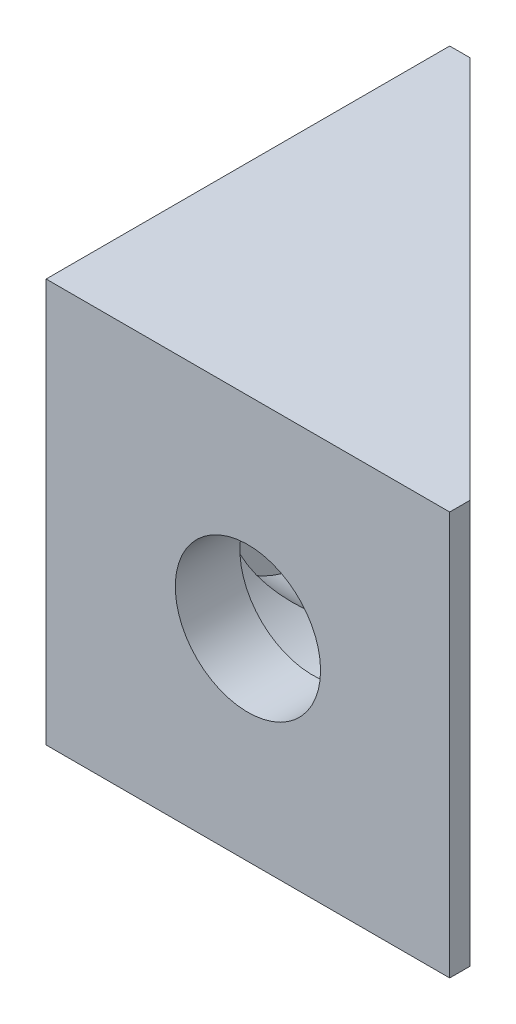
SolidWorks part; units mm, degrees
ref_plane "Front Plane" through (0, 0, 0) normal (0, 0, 1) x (1, 0, 0)
ref_plane "Top Plane" through (0, 0, 0) normal (0, 1, 0) x (1, 0, 0)
ref_plane "Right Plane" through (0, 0, 0) normal (1, 0, 0) x (0, 0, -1)
sketch "Sketch2" plane through (0, 0, 0) normal (0, 1, 0) x (1, 0, 0)
  line L0 (0, 0) -> (0, 20)
  line L2 (20, 0) -> (0, 0)
  line L3 (0, 20) -> (1, 20)
  line L4 (20, 0) -> (20, 1)
  line L5 (1, 20) -> (20, 1)
  dimension "D1" = 20
  dimension "D2" = 1
extrude "Boss-Extrude1" add sketch "Sketch2" along normal mid plane 20
sketch "Sketch3" plane through (0, 0, 0) normal (0, 0, 1) x (1, 0, 0)
  line L0 (0, 10) -> (20, -10) construction
  line L1 (20, 10) -> (0, 0) construction
  circle A0 centre (10, 0) radius 3.6
  circle A1 centre (10, 0) radius 5.5
  dimension "D1" = 7.2
  dimension "D2" = 11
extrude "Cut-Extrude1" cut sketch "Sketch3" against normal up to surface (7.4 mm away) contours A0 region at (10, 0, 0) up to face at (10.5, 0, -10.5)
extrude "Cut-Extrude3" cut sketch "Sketch3<4>" against normal up to surface (4.2 mm away) from offset 3.2 up to face at (13.6, 0, -7.4) offset against normal yes
sketch "Sketch3<4>" plane through (0, 0, 0) normal (0, 0, 1) x (1, 0, 0) same geometry as "Sketch3"
sketch "Sketch4" plane through (0, 0, 0) normal (-1, 0, 0) x (0, 0, 1)
  line L0 (-20, 10) -> (0, -10) construction
  line L1 (0, 10) -> (-20, -10) construction
  circle A0 centre (-10, 0) radius 3.6
  circle A1 centre (-10, 0) radius 5.5
  point P11 (-10, 0)
  dimension "D1" = 7.2
  dimension "D2" = 11
extrude "Cut-Extrude2" cut sketch "Sketch4" against normal up to surface (14.6 mm away) contours A0 region at (0, 0, -10) up to face at (15.5, 0, -5.5)
extrude "Cut-Extrude4" cut sketch "Sketch4<3>" against normal up to surface (11.4 mm away) from offset 3.2 up to face at (15.5, 0, -5.5) offset against normal yes
sketch "Sketch4<3>" plane through (0, 0, 0) normal (-1, 0, 0) x (0, 0, 1) same geometry as "Sketch4"
